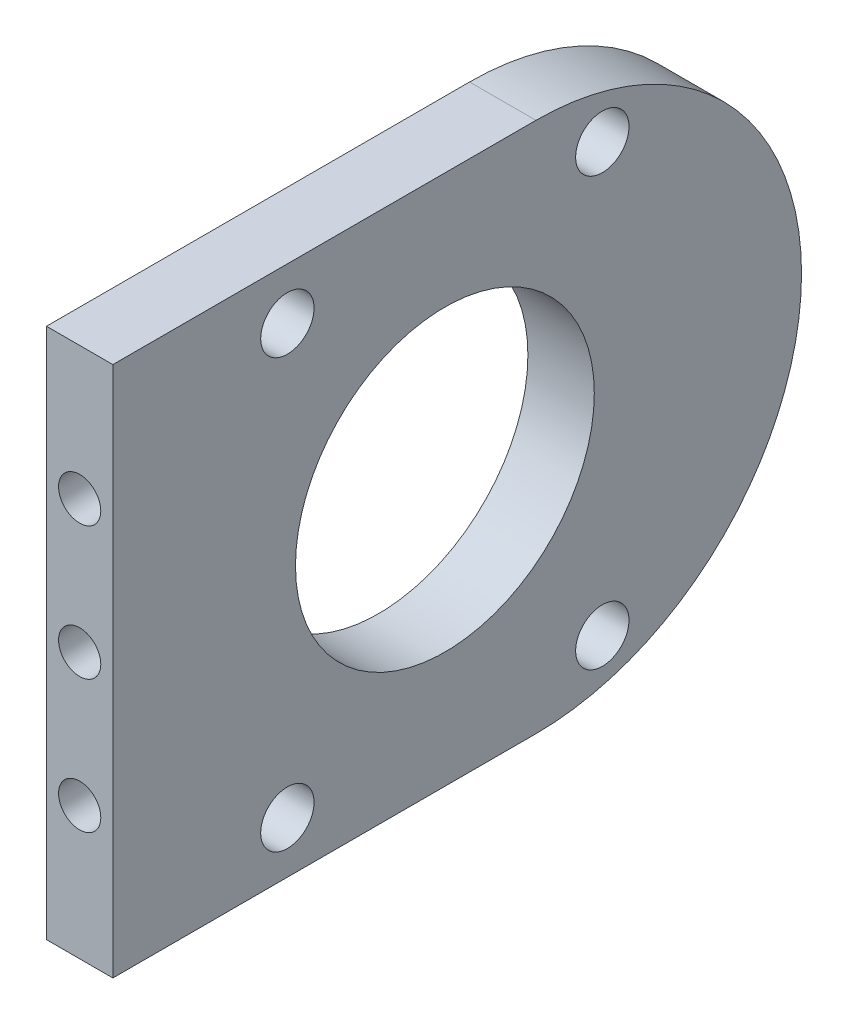
SolidWorks part; units mm, degrees
material "6061-T6 (SS)"
ref_plane "Front" through (0, 0, 0) normal (0, 0, 1) x (1, 0, 0)
ref_plane "Top" through (0, 0, 0) normal (0, 1, 0) x (1, 0, 0)
ref_plane "Right" through (0, 0, 0) normal (1, 0, 0) x (0, 0, -1)
sketch "Sketch2" plane through (0, 0, 0) normal (1, 0, 0) x (0, 0, -1)
  line L1 (-38.1, -25.4) -> (38.1, -25.4)
  line L2 (-38.1, -25.4) -> (-38.1, 25.4)
  line L3 (-38.1, 25.4) -> (38.1, 25.4)
  line L4 (38.1, -25.4) -> (38.1, 25.4)
  line L5 (-38.1, -25.4) -> (38.1, 25.4) construction
  line L6 (-38.1, 25.4) -> (38.1, -25.4) construction
  point P0 (0, 0)
  dimension "D1" = 76.2
  dimension "D2" = 50.8
extrude "Boss-Extrude2" add sketch "Sketch2" along normal blind 6.35
hole_wizard "#10-32 Tapped Hole1" positions "Sketch3" profile "Sketch5" tap size "#10-32" standard "ANSI Inch"
sketch "Sketch3" plane through (0, 0, 38.1) normal (0, 0, 1) x (1, 0, 0)
  line L0 (3.175, 25.4) -> (3.175, 12.7) construction
  line L1 (6.35, 25.4) -> (0, 25.4) construction
  line L3 (3.175, 12.7) -> (3.175, 0) construction
  line L4 (3.175, 0) -> (3.175, -12.7) construction
  line L5 (3.175, -12.7) -> (3.175, -25.4) construction
  line L6 (6.35, -25.4) -> (0, -25.4) construction
  point P0 (3.175, -12.7)
  point P2 (3.175, 0)
  point P6 (3.175, 12.7)
sketch "Sketch5" plane through (3.175, -12.7, 38.1) normal (1, 0, 0) x (0, -1, 0)
  line L0 (0, 0) -> (0, 13.2428)
  line L1 (0, 13.2428) -> (2.0193, 12.0294)
  line L2 (2.0193, 12.0294) -> (2.0193, 0)
  line L5 (2.0193, 0) -> (0, 0)
  line L10 (0, 13.2428) -> (-2.0193, 12.0294) construction
  line L11 (0, -6.35) -> (0, 107.95) construction
  dimension "Tap Drill Dia." = 4.0386
  dimension "Tap Drill Depth" = 12.0294
  dimension "Drill Angle" = 118
cosmetic thread "Hole Thread1" parameters "D1"=9.652, "D2"=4.826
cosmetic thread "Hole Thread3" parameters "D1"=9.652, "D2"=4.826
cosmetic thread "Hole Thread4" parameters "D1"=9.652, "D2"=4.826
sketch "Sketch6" plane through (6.35, 0, 0) normal (1, 0, 0) x (0, 0, -1)
  line L0 (-38.1, 25.4) -> (-38.1, -25.4) construction
  line L1 (-38.1, -25.4) -> (38.1, -25.4) construction
  circle A0 centre (-6.35, 0) radius 14.2875
  dimension "D1" = 31.75
  dimension "D3" = 28.575
  dimension "D2" = 25.4
extrude "Cut-Extrude1" cut sketch "Sketch6" against normal through all
sketch "Sketch10" plane through (0, 0, 0) normal (-1, 0, 0) x (0, 0, 1)
  line L0 (0, 0) -> (12.5444, 0) construction
  point P3 (-8.7041, -20.4408)
  point P8 (21.4132, 20.4687)
  point P16 (21.4132, -20.4687)
  point P17 (-8.7041, 20.4408)
hole_wizard "#10 Clearance Hole1" positions "Sketch10" profile "Sketch9" hole size "#10" standard "ANSI Inch" end condition through all
sketch "Sketch9" plane through (0, -20.4408, -8.7041) normal (0, 1, 0) x (0, 0, 1)
  line L0 (0, 0) -> (0, 6.35)
  line L1 (0, 6.35) -> (2.5527, 6.35)
  line L2 (2.5527, 6.35) -> (2.5527, 0)
  line L5 (2.5527, 0) -> (0, 0)
  line L11 (0, -6.35) -> (0, 107.95) construction
  dimension "Thru Hole Dia." = 5.1054
  dimension "Thru Hole Depth" = 6.35
sketch "Sketch13" plane through (6.35, 0, 0) normal (1, 0, 0) x (0, 0, -1)
  line L0 (27.7541, -25.4) -> (27.7541, 25.4)
  line L1 (-38.1, -25.4) -> (38.1, -25.4) construction
  line L2 (38.1, 25.4) -> (-38.1, 25.4) construction
  line L3 (27.7541, 25.4) -> (38.1, 25.4)
  line L4 (38.1, 25.4) -> (38.1, -25.4)
  line L5 (38.1, -25.4) -> (27.7541, -25.4)
  circle A0 centre (8.7041, -20.4408) radius 2.5527 construction
  dimension "D1" = 19.05
extrude "Cut-Extrude2" cut sketch "Sketch13" against normal through all
fillet "Fillet3" radius 25.4 2 edges at (3.175, 25.4, -27.7541) (3.175, -25.4, -27.7541)
